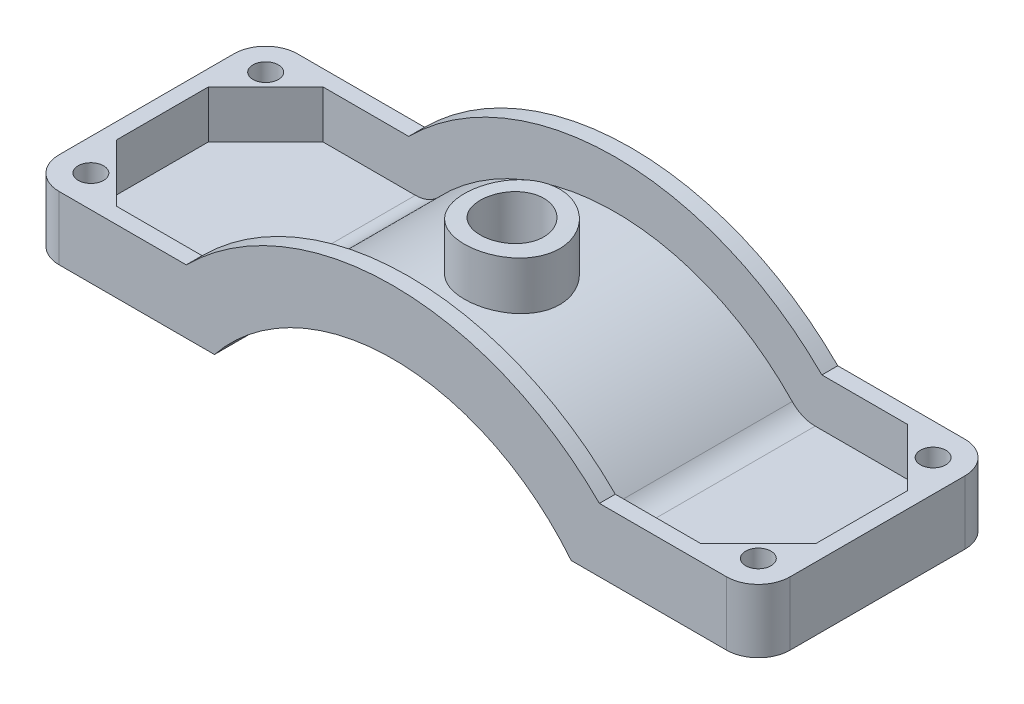
SolidWorks part; units mm, degrees
ref_plane "정면" through (0, 0, 0) normal (0, 0, 1) x (1, 0, 0)
ref_plane "윗면" through (0, 0, 0) normal (0, 1, 0) x (1, 0, 0)
ref_plane "우측면" through (0, 0, 0) normal (1, 0, 0) x (0, 0, -1)
sketch "스케치2" plane through (0, 0, 0) normal (0, 0, 1) x (1, 0, 0)
  line L0 (0, 0) -> (58.8813, 0)
  line L1 (230, 0) -> (230, 20)
  line L2 (230, 20) -> (180, 20)
  line L3 (0, 0) -> (0, 20)
  line L4 (0, 20) -> (50, 20)
  line L5 (171.1187, 0) -> (230, 0)
  arc A0 (180, 20) -> (50, 20) centre (115, -45.1076) ccw
  arc A1 (180.9052, 20) -> (49.0948, 20) centre (115, -45.1076) ccw
  arc A2 (171.1187, 0) -> (58.8813, 0) centre (115, -45.1076) ccw
  dimension "D1" = 130
  dimension "D2" = 184
  dimension "D5" = 50
  dimension "D3" = 20
  dimension "D4" = 20
extrude "보스-돌출1" add sketch "스케치2" along normal blind 75 contours L4 A0 L2 L1 L5 A2 L0 L3
shell "쉘1" thickness 5 removed face at (205, 20, 37.5) removed face at (115, 33.4462, 37.5) removed face at (25, 20, 37.5)
fillet "필렛1" radius 10 2 edges at (173.4656, 5, 37.5) (56.5344, 5, 37.5)
sketch "스케치3" plane through (0, 20, 0) normal (0, 1, 0) x (1, 0, 0)
  line L1 (0, -75) -> (0, 0) construction
  line L2 (0, 0) -> (50, 0) construction
  line L3 (24.8906, 0) -> (0, 0)
  line L4 (0, 0) -> (0, -24.8906)
  line L5 (115, 0) -> (115, -86.1177) construction
  line L6 (180, 0) -> (50, 0) construction
  line L7 (0, -37.5) -> (230, -37.5) construction
  line L8 (230, -75) -> (230, 0) construction
  line L9 (230, 0) -> (230, -24.8906)
  line L10 (205.1094, 0) -> (230, 0)
  line L12 (205.1094, -75) -> (230, -75)
  line L13 (230, -75) -> (230, -50.1094)
  line L16 (0, -75) -> (0, -50.1094)
  line L17 (24.8906, -75) -> (0, -75)
  line L18 (5, -23.0135) -> (23.0135, -5)
  line L19 (5, -70) -> (5, -5) construction
  line L20 (5, -5) -> (52.1027, -5) construction
  line L21 (23.0135, -5) -> (5, -5)
  line L22 (5, -5) -> (5, -23.0135)
  line L23 (225, -23.0135) -> (206.9865, -5)
  line L24 (225, -5) -> (225, -23.0135)
  line L25 (206.9865, -5) -> (225, -5)
  line L26 (225, -70) -> (225, -51.9865)
  line L27 (206.9865, -70) -> (225, -70)
  line L28 (225, -51.9865) -> (206.9865, -70)
  line L29 (5, -70) -> (5, -51.9865)
  line L30 (23.0135, -70) -> (5, -70)
  line L31 (5, -51.9865) -> (23.0135, -70)
  line M9 (5, -70) -> (5, -5)
  line M10 (5, -5) -> (50, -5)
  line M12 (50, 0) -> (0, 0)
  line M13 (0, 0) -> (0, -75)
  line M14 (0, -75) -> (50, -75)
  line M16 (50, -70) -> (5, -70)
extrude "보스-돌출2" add sketch "스케치3" against normal blind 20 contours M13 M9 M10 M12 | M9 M10 | M13 M14 M16 M9 | M9 M16 | L13 L12 | L9 L10 region at (11.0045, 20, 11.0045) region at (11.0045, 20, 63.9955)
sketch "스케치4" plane through (0, 20, 0) normal (0, 1, 0) x (1, 0, 0)
  point P0 (6.0671, -5.6974)
fillet "필렛2" radius 10 4 edges at (230, 10, 0) (230, 10, 75) (0, 10, 0) (0, 10, 75)
sketch "스케치5" plane through (0, 20, 0) normal (0, 1, 0) x (1, 0, 0)
  line L0 (0, -65) -> (0, -10) construction
  line L1 (10, 0) -> (50, 0) construction
  line L2 (115, 0) -> (115, -75) construction
  line L3 (180, 0) -> (50, 0) construction
  line L4 (50, -75) -> (180, -75) construction
  line L5 (0, -37.5) -> (230, -37.5) construction
  line L6 (230, -65) -> (230, -10) construction
  circle A0 centre (10, -10) radius 4
  circle A1 centre (10, -65) radius 4
  circle A2 centre (220, -65) radius 4
  circle A3 centre (220, -10) radius 4
  point P0 (10, -10)
  point P15 (10, -65)
  point P16 (220, -10)
  point P17 (220, -65)
  dimension "D1" = 10
  dimension "D2" = 10
extrude "보스-돌출3" add sketch "스케치3<3>" against normal blind 20 contours L25 L23 L24 | L26 L28 L27 region at (218.9955, 20, 11.0045) region at (218.9955, 20, 63.9955)
sketch "스케치3<3>" plane through (0, 20, 0) normal (0, 1, 0) x (1, 0, 0) same geometry as "스케치3"
extrude "컷-돌출1" cut sketch "스케치5" against normal blind 15 contours A0 | A3 | A2 | A1 region at (10, 20, 10) region at (220, 20, 65) region at (220, 20, 10)
ref_plane "평면1" through (0, 34, 0) normal (0, 1, 0) x (1, 0, 0)
sketch "스케치6" plane through (0, 34, 0) normal (0, 1, 0) x (1, 0, 0)
  line L0 (0, -37.5) -> (230, -37.5) construction
  circle A0 centre (115, -37.5) radius 15
  circle A1 centre (115, -37.5) radius 10
  dimension "D1" = 30
  dimension "D2" = 20
extrude "보스-돌출4" add sketch "스케치6" along normal blind 15 and the other way blind 5 separate body
extrude "컷-돌출2" cut sketch "스케치6<3>" against normal blind 15 contours A1
sketch "스케치6<3>" plane through (0, 34, 0) normal (0, 1, 0) x (1, 0, 0) same geometry as "스케치6"
sketch "스케치7" plane through (0, 0, 75) normal (0, 0, 1) x (1, 0, 0)
  line L1 (50, 20) -> (50, 85.4854)
  line L2 (180, 20) -> (180, 85.4854)
  line L3 (50, 85.4854) -> (180, 85.4854)
  arc M4 (180, 20) -> (50, 20) centre (115, -45.1076) ccw
extrude "컷-돌출3" cut sketch "스케치7" against normal blind 274 and the other way through all contours L3 L1 L2 M4 region at (115, 61.3594, 75)
